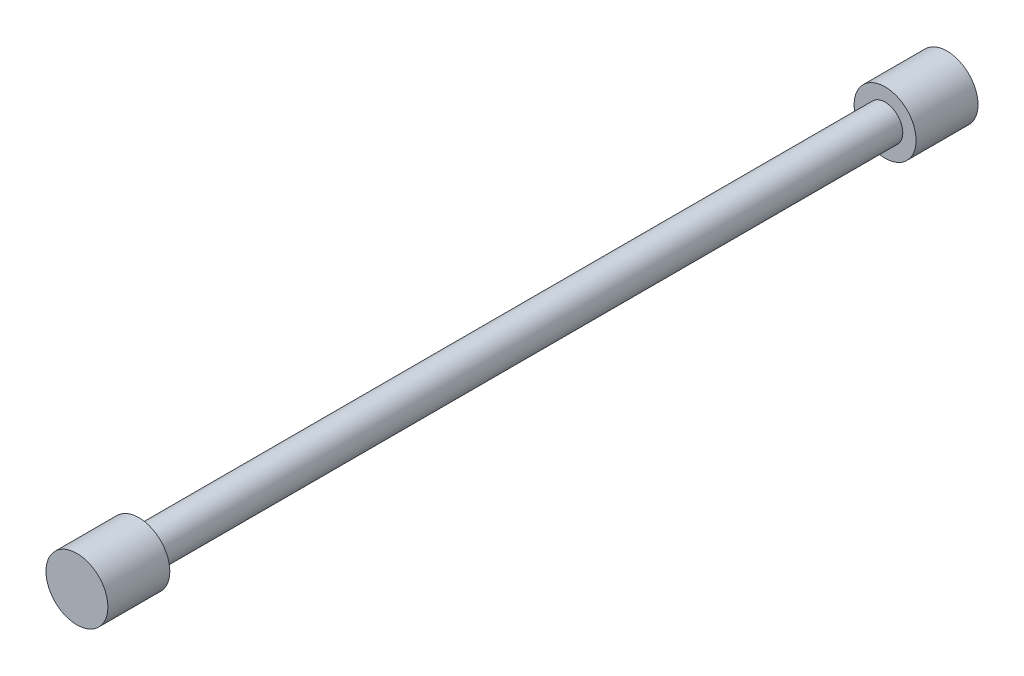
SolidWorks part; units mm, degrees
material "AISI 1045 Steel, cold drawn"
ref_plane "Front Plane" through (0, 0, 0) normal (0, 0, 1) x (1, 0, 0)
ref_plane "Top Plane" through (0, 0, 0) normal (0, 1, 0) x (1, 0, 0)
ref_plane "Right Plane" through (0, 0, 0) normal (1, 0, 0) x (0, 0, -1)
sketch "SK_Rod" plane through (0, 0, 0) normal (0, 1, 0) x (1, 0, 0)
  line L0 (0, -10) -> (0, 192.6691) construction
  line L1 (0, -7) -> (7, -7)
  line L2 (7, -7) -> (7, 7)
  line L3 (7, 7) -> (4, 7)
  line L4 (4, 7) -> (4, 175.6691)
  line L5 (4, 175.6691) -> (7, 175.6691)
  line L6 (7, 175.6691) -> (7, 189.6691)
  line L7 (7, 189.6691) -> (0, 189.6691)
  line L8 (0, 189.6691) -> (0, -7)
  dimension "P1" = 10
  dimension "P2" = 192.6691
  dimension "P3" = 7
  dimension "P4" = 7
  dimension "P5" = 7
  dimension "P6" = 7
  dimension "P7" = 7
  dimension "P8" = 4
  dimension "P9" = 7
  dimension "P10" = 4
  dimension "P11" = 175.6691
  dimension "P12" = 7
  dimension "P13" = 175.6691
  dimension "P14" = 7
  dimension "P15" = 189.6691
  dimension "P16" = 189.6691
revolve "Rod_Body" add sketch "SK_Rod" angle 360 about L0
sketch "SK_Ends" plane through (0, 0, 0) normal (0, 1, 0) x (1, 0, 0)
  point P0 (0, 0)
  point P2 (0, 182.6691)
  dimension "P1" = 182.6691
equation "\"Rod_length\"= 182.669"
